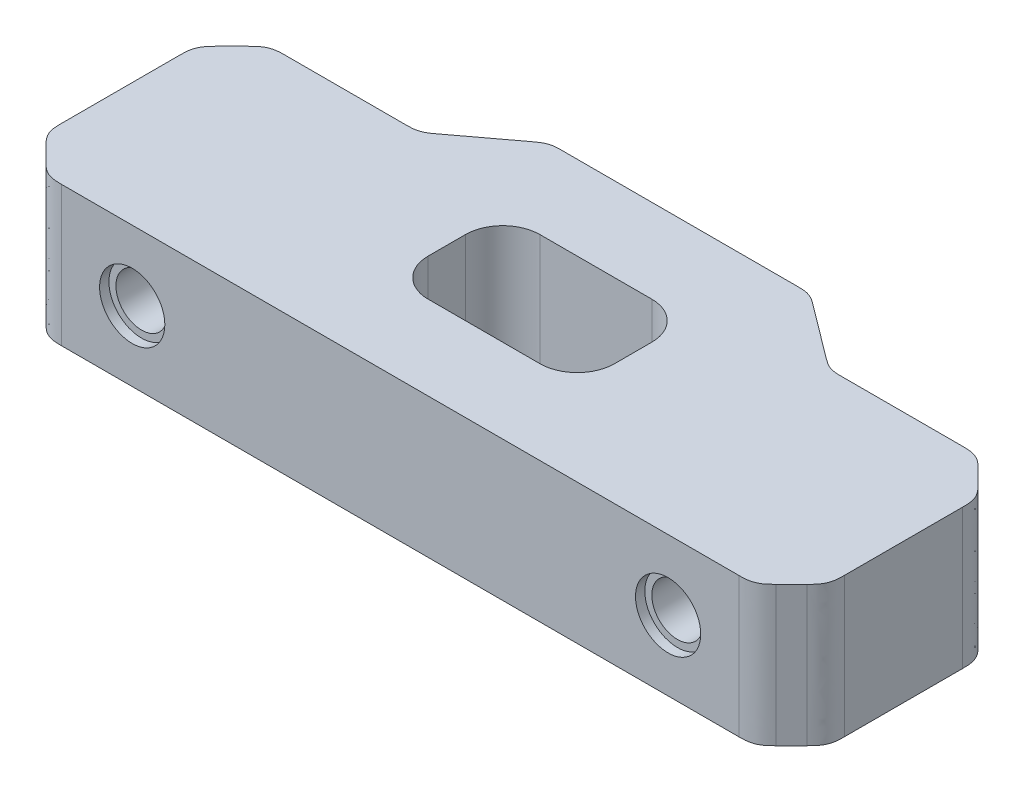
SolidWorks part; units mm, degrees
ref_plane "Plan de face" through (0, 0, 0) normal (0, 0, 1) x (1, 0, 0)
ref_plane "Plan de dessus" through (0, 0, 0) normal (0, 1, 0) x (1, 0, 0)
ref_plane "Plan de droite" through (0, 0, 0) normal (1, 0, 0) x (0, 0, -1)
sketch "Esquisse1" plane through (0, 0, 0) normal (0, 1, 0) x (1, 0, 0)
  line L9 (-42, 8) -> (-42, 0)
  line L10 (-42, 0) -> (-42, -8)
  line L11 (-42, -8) -> (-38, -8) construction
  line L12 (-38, -8) -> (-38, -12) construction
  line L19 (-22, 12) -> (-14, 18)
  line L20 (-38, -12) -> (-42, -8)
  line L22 (0, 0) -> (0, 20) construction
  line L23 (0, 0) -> (0, -12) construction
  line L24 (-30, 0) -> (1, 0) construction
  line L25 (0, -55) -> (0, 55) construction
  line L26 (-10, -3) -> (10, -3)
  line L36 (0, 20) -> (0, 9) construction
  line L42 (0, -12) -> (0, 18) construction
  line L45 (-10, 9) -> (-10, -3)
  line L56 (-10, 9) -> (10, 9)
  line L57 (-14, 18) -> (14, 18)
  line L58 (22, 12) -> (14, 18)
  line L59 (38, 8) -> (38, 12) construction
  line L60 (42, 8) -> (38, 8) construction
  line L61 (42, 8) -> (38, 12)
  line L62 (38, 12) -> (22, 12)
  line L63 (42, 8) -> (42, 0)
  line L64 (10, 9) -> (10, -3)
  line L71 (-42, 8) -> (-38, 8) construction
  line L72 (-38, 8) -> (-38, 12) construction
  line L73 (-38, -12) -> (38, -12)
  line L74 (-38, 12) -> (-22, 12)
  line L75 (-42, 8) -> (-38, 12)
  line L76 (38, -8) -> (38, -12) construction
  line L77 (42, -8) -> (38, -8) construction
  line L78 (38, -12) -> (42, -8)
  line L79 (42, 0) -> (42, -8)
  circle A0 centre (-30, 0) radius 4
  circle A3 centre (30, 0) radius 4
  point P36 (0, -3)
  point P39 (0, -3)
  dimension "D4" = 4
  dimension "D5" = 8
  dimension "D6" = 4
  dimension "D15" = 30
  dimension "D2" = 8
  dimension "D3" = 8
  dimension "D7" = 14
  dimension "D8" = 9
  dimension "D11" = 9
  dimension "D13" = 10
extrude "Boss.-Extru.1" add sketch "Esquisse1" along normal blind 15 contours L19 L9 L10 L56 L64 L26 L45 A0 | A0 | A3 region at (-39.3693, 0, -9.3693) region at (-30, 0, 0) region at (30, 0, 0)
fillet "Congé1" radius 4 12 edges at (42, 7.5, 8) (38, 7.5, 12) (42, 7.5, -8) (38, 7.5, -12) (22, 7.5, -12) (14, 7.5, -18) (-14, 7.5, -18) (-22, 7.5, -12) (-38, 7.5, -12) (-42, 7.5, -8) (-42, 7.5, 8) (-38, 7.5, 12) curvature continuous yes
extrude "Enlèv. mat.-Extru.1" cut sketch "Esquisse1<4>" along normal blind 12 contours A0 | A3 region at (-30, 0, 0) region at (30, 0, 0)
sketch "Esquisse1<4>" plane through (0, 0, 0) normal (0, 1, 0) x (1, 0, 0) same geometry as "Esquisse1"
fillet "Congé2" radius 4 4 edges at (10, 7.5, 3) (-10, 7.5, 3) (10, 7.5, -9) (-10, 7.5, -9)
sketch "Esquisse2" plane through (0, 0, 12) normal (0, 0, 1) x (1, 0, 0)
  line L0 (0, 0) -> (0, 15) construction
  line L2 (26, 7.5) -> (-26, 7.5) construction
  line L3 (-36.3431, 15) -> (36.3431, 15) construction
  line L4 (0, -8.305) -> (0, 8.305) construction
  line L5 (26, 7.5) -> (31.5, 7.5) construction
  circle A0 centre (-28.75, 7.5) radius 2.75
  circle A1 centre (28.75, 7.5) radius 2.75
  point P14 (0, 7.5)
  dimension "D2" = 5.5
  dimension "D1" = 26
extrude "Enlèv. mat.-Extru.2" cut sketch "Esquisse2" against normal blind 10 and the other way through all
sketch "Esquisse4" plane through (0, 0, 12) normal (0, 0, 1) x (1, 0, 0)
  line L0 (26, 7.5) -> (31.5, 7.5) construction
  arc A0 (26.5359, 9.131) -> (26.5359, 5.869) centre (28.75, 7.5) ccw construction
  arc A1 (26.5359, 5.869) -> (26.5359, 9.131) centre (28.75, 7.5) ccw construction
  circle A2 centre (28.75, 7.5) radius 3.5
  dimension "D1" = 7
extrude "Enlèv. mat.-Extru.3" cut sketch "Esquisse4" against normal blind 1
sketch "Esquisse5" plane through (0, 0, 12) normal (0, 0, 1) x (1, 0, 0)
  line L0 (-28.75, 10.25) -> (-28.75, 4.75) construction
  circle A0 centre (-28.75, 7.5) radius 2.75 construction
  arc A1 (-26.5359, 9.131) -> (-26.5359, 5.869) centre (-28.75, 7.5) ccw construction
  circle A2 centre (-28.75, 7.5) radius 3.5
  dimension "D1" = 7
extrude "Enlèv. mat.-Extru.4" cut sketch "Esquisse5" against normal blind 1
